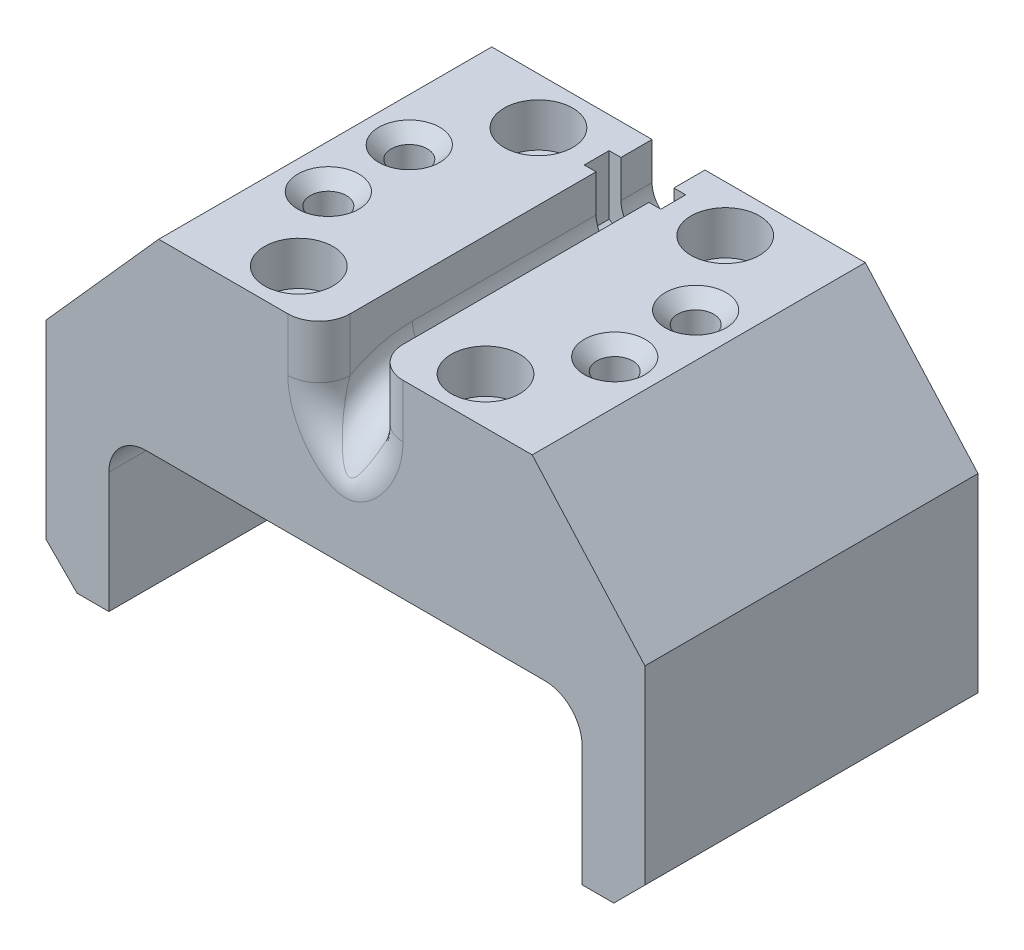
SolidWorks part; units mm, degrees
material "PET"
ref_plane "Front Plane" through (0, 0, 0) normal (0, 0, 1) x (1, 0, 0)
ref_plane "Top Plane" through (0, 0, 0) normal (0, 1, 0) x (1, 0, 0)
ref_plane "Right Plane" through (0, 0, 0) normal (1, 0, 0) x (0, 0, -1)
sketch "Sketch1" plane through (0, 0, 0) normal (0, 0, 1) x (1, 0, 0)
  line L0 (0, 19.0297) -> (0, -2.5925) construction
  line L1 (-12.9623, 0) -> (13.1829, 0) construction
  line L2 (48.1, 6) -> (-48.1, 6)
  line L3 (-48.1, 6) -> (-48.1, -49.8)
  line L4 (-48.1, -49.8) -> (-38, -49.8)
  line L5 (-38, -49.8) -> (-38, -24.4)
  line L6 (-38, -24.4) -> (38, -24.4)
  line L7 (48.1, -49.8) -> (38, -49.8)
  line L8 (38, -49.8) -> (38, -24.4)
  line L9 (48.1, 6) -> (48.1, -49.8)
  circle A0 centre (0, 0) radius 3.75 construction
  point P16 (0, -24.4)
  point P17 (0, 6)
  dimension "D1" = 7.5
  dimension "D2" = 6
  dimension "D6" = 24.4
  dimension "D3" = 96.2
  dimension "D4" = 25.4
  dimension "D5" = 76
extrude "Boss-Extrude1" add sketch "Sketch1" along normal mid plane 53.5
sketch "Sketch9" plane through (0, 0, 26.75) normal (0, 0, 1) x (1, 0, 0)
  line L0 (0, 0) -> (0, -24.4) construction
  line L1 (-38, -24.4) -> (38, -24.4) construction
  line L2 (-30, 6) -> (-48.1, -14.3)
  line L3 (48.1, 6) -> (-48.1, 6) construction
  line L4 (-48.1, 6) -> (-48.1, -49.8) construction
  line L5 (-48.1, -14.3) -> (-48.1, 6)
  line L6 (-48.1, 6) -> (-30, 6)
  line L7 (-38, -24.4) -> (-48.1, -24.4) construction
  line L8 (-48.1, -24.4) -> (-48.1, -14.3) construction
  line L9 (48.1, 6) -> (30, 6)
  line L10 (48.1, -14.3) -> (48.1, 6)
  line L11 (30, 6) -> (48.1, -14.3)
  dimension "D1" = 30
extrude "Cut-Extrude8" cut sketch "Sketch9" against normal through all
fillet "Fillet1" radius 6 2 edges at (38, -24.4, 0) (-38, -24.4, 0)
sketch "Sketch2" plane through (0, 6, 0) normal (0, 1, 0) x (1, 0, 0)
  line L0 (0, 35.9356) -> (0, 6.1551) construction
  line L1 (-23, 6.5) -> (-23, -6.5) construction
  line L3 (30, 26.75) -> (-30, 26.75) construction
  line L4 (0, 0) -> (-48.1, 0) construction
  line L5 (-48.1, 26.75) -> (-48.1, -26.75) construction
  circle A2 centre (-23, 6.5) radius 2.9
  circle A3 centre (-23, -6.5) radius 2.9
  circle A4 centre (-15, 19.25) radius 3.05
  circle A5 centre (23, -6.5) radius 2.9
  circle A6 centre (23, 6.5) radius 2.9
  circle A7 centre (15, 19.25) radius 3.05
  circle A8 centre (15, -19.25) radius 3.05
  circle A9 centre (-15, -19.25) radius 3.05
  point P13 (-23, 0)
  dimension "D2" = 5.8
  dimension "D4" = 6.1
  dimension "D5" = 13
  dimension "D6" = 23
  dimension "D9" = 7.5
  dimension "D10" = 15
extrude "Cut-Extrude1" cut sketch "Sketch2" against normal blind 22
sketch "Sketch3" plane through (0, 6, 0) normal (0, 1, 0) x (1, 0, 0)
  circle A0 centre (-15, 19.25) radius 5.5
  circle A1 centre (15, 19.25) radius 5.5
  circle A2 centre (-15, -19.25) radius 5.5
  circle A3 centre (15, -19.25) radius 5.5
  dimension "D1" = 11
extrude "Cut-Extrude2" cut sketch "Sketch3" against normal blind 7
sketch "Sketch4" plane through (0, 0, -26.75) normal (0, 0, -1) x (-1, 0, 0)
  circle A0 centre (0, 0) radius 4.25
  dimension "D1" = 8.5
extrude "Cut-Extrude3" cut sketch "Sketch4" against normal through all
sketch "Sketch5" plane through (0, 0, -26.75) normal (0, 0, -1) x (-1, 0, 0)
  line L1 (-6.15, 3.5507) -> (-6.15, 8.956)
  line L2 (6.15, -3.5507) -> (6.15, 3.5507)
  line L3 (6.15, 3.5507) -> (0, 7.1014) construction
  line L4 (0, 7.1014) -> (-6.15, 3.5507) construction
  line L5 (-6.15, 3.5507) -> (-6.15, -3.5507)
  line L6 (-6.15, -3.5507) -> (0, -7.1014)
  line L7 (0, -7.1014) -> (6.15, -3.5507)
  line L8 (-6.15, 8.956) -> (6.15, 8.956)
  line L9 (6.15, 8.956) -> (6.15, 3.5507)
  circle A0 centre (0, 0) radius 6.15 construction
  dimension "D1" = 12.3
extrude "Cut-Extrude4" cut sketch "Sketch5" against normal blind 4 from offset 5 offset against normal yes
chamfer "Chamfer2" distance 5 angle 45 2 edges at (48.1, -49.8, 0) (-48.1, -49.8, 0)
sketch "Sketch10" plane through (0, 0, -26.75) normal (0, 0, -1) x (-1, 0, 0)
  line L0 (-30, 6) -> (30, 6) construction
  line L1 (-4.25, 0) -> (4.25, 0)
  line L2 (-4.25, 0) -> (-4.25, 6)
  line L3 (-4.25, 6) -> (4.25, 6)
  line L4 (4.25, 0) -> (4.25, 6)
  circle A0 centre (0, 0) radius 4.25 construction
extrude "Cut-Extrude9" cut sketch "Sketch10" against normal through all
sketch "Sketch12" plane through (0, -16, 0) normal (0, 1, 0) x (1, 0, 0)
  circle A0 centre (15, -19.25) radius 3.05 construction
  circle A1 centre (-15, -19.25) radius 3.05 construction
  circle A2 centre (-15, 19.25) radius 3.05 construction
  circle A3 centre (15, 19.25) radius 3.05 construction
  circle A4 centre (15, -19.25) radius 3.05
  circle A5 centre (-15, -19.25) radius 3.05
  circle A6 centre (-15, 19.25) radius 3.05
  circle A7 centre (15, 19.25) radius 3.05
extrude "Cut-Extrude10" cut sketch "Sketch12" against normal through all
chamfer "Chamfer3" distance 2 angle 45 4 edges at (-25.9, 6, 6.5) (-25.9, 6, -6.5) (25.9, 6, -6.5) (25.9, 6, 6.5)
ref_plane "Plane1" through (0, 0, 11.75) normal (0, 0, 1) x (1, 0, 0)
sketch "Sketch13" plane through (0, 0, 11.75) normal (0, 0, 1) x (1, 0, 0)
  line L0 (-4.25, 0) -> (-4.25, 6) construction
  line L1 (4.25, 6) -> (4.25, 0) construction
  line L2 (-4.25, 0) -> (-4.25, 6)
  line L3 (4.25, 6) -> (4.25, 0)
  line L4 (-4.25, 6) -> (4.25, 6)
  line L5 (-69.3335, -20.8334) -> (63.4825, -20.8334) construction
  arc A0 (-4.25, 0) -> (4.25, 0) centre (0, 0) ccw construction
  arc A1 (-4.25, 0) -> (4.25, 0) centre (0, 0) ccw
revolve "Cut-Revolve1" cut sketch "Sketch13" angle 90 about L5
fillet "Fillet2" radius 5 3 edges at (4.25, -0.1877, 26.75) (-4.25, -0.1877, 26.75) (0.1267, -0.7316, 26.75)
equation "\"M5_tap\"=4.2mm       ' Below you can do mesurements as follows: cm, mm, ft, in, m, "
equation "\"M5_clearence\"=5.5mm"
equation "\"M6_tap\"=5mm"
equation "\"M6_clearence\"=6.6mm"
equation "\"work_area_width\"=1100mm"
equation "\"work_area_depth\"=900mm"
equation "\"steel_base_width\"=3in "
equation "\"steel_base_height\"=2in"
equation "\"steel_base_wall_thickness\"=0.125in"
equation "\"steel_base_radius\"=6mm"
equation "\"steel_sides_width\"=3in     'this tube is rotated so flip width/height"
equation "\"steel_sides_height\"=2in    'this tube is rotated so flip width/height"
equation "\"steel_sides_wall_thickness\"=0.125in"
equation "\"steel_sides_radius\"=6mm"
equation "\"steel_gantry_width\"=4in    'this tube is rotated so flip width/height"
equation "\"steel_gantry_height\"=3in    'this tube is rotated so flip width/height"
equation "\"steel_gantry_wall_thickness\"=0.125in"
equation "\"steel_gantry_radius\"=6mm"
equation "\"steel_rollers_width\"=3in"
equation "\"steel_rollers_height\"=2in    'keep as low as possible as this increases how big plastic parts are"
equation "\"steel_rollers_wall_thickness\"=0.125in"
equation "\"steel_rollers_radius\"=6mm"
equation "\"steel_zbox_width\"=4in     'if the gantry height (rotated) is too thick, a wider zbox is necessary"
equation "\"steel_zbox_height\"=2in     'hole patteren changes as the zbox and gantry height (rotated) changes."
equation "\"steel_zbox_wall_thickness\"=0.125in"
equation "\"steel_zbox_radius\"=6mm"
equation "\"alu_zangle_width\"=4in     'check that it doesn't interfer with the gantry"
equation "\"alu_zangle_height\"=4in"
equation "\"alu_zangle_wall_thickness\"=0.375in   'check that it doesn't interfer with the gantry"
equation "\"D6@Sketch1\"=\"steel_zbox_height\" /2 -1"
equation "\"D4@Sketch1\"=\"steel_rollers_width\"/3"
equation "\"D3@Sketch1\"=\"steel_gantry_height\" + 20mm"
